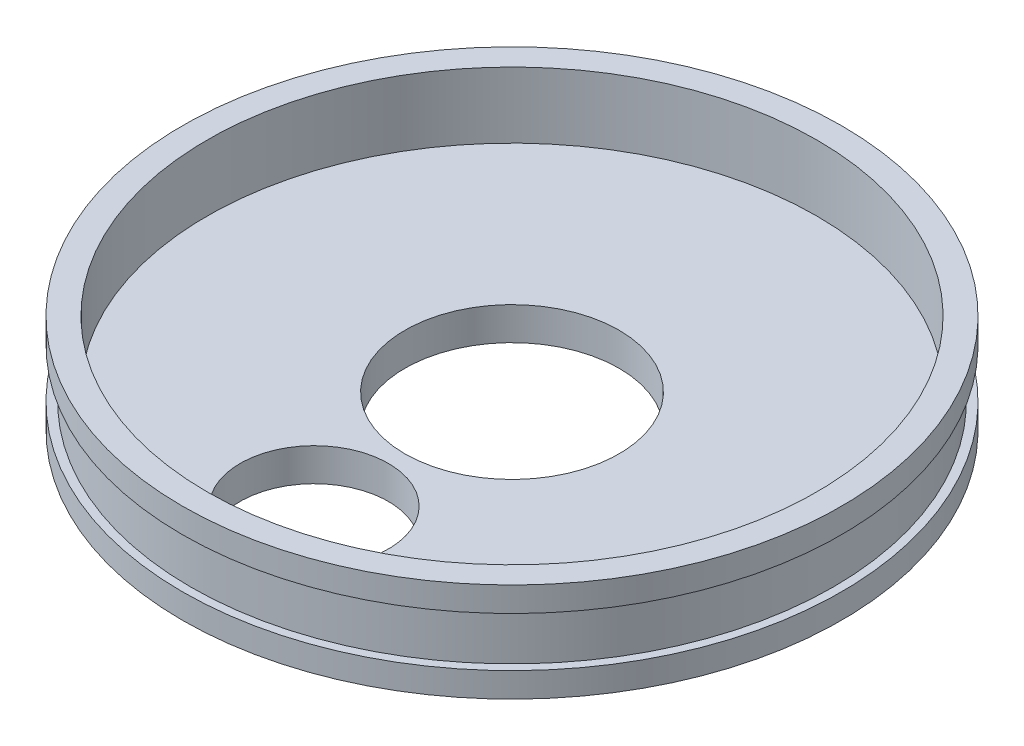
SolidWorks part; units mm, degrees
ref_plane "Front Plane" through (0, 0, 0) normal (0, 0, 1) x (1, 0, 0)
ref_plane "Top Plane" through (0, 0, 0) normal (0, 1, 0) x (1, 0, 0)
ref_plane "Right Plane" through (0, 0, 0) normal (1, 0, 0) x (0, 0, -1)
sketch "Sketch2" plane through (0, 0, 0) normal (0, 1, 0) x (1, 0, 0)
  line L0 (0, 0) -> (0, -12) construction
  circle A0 centre (0, 0) radius 18.5
  circle A1 centre (0, 0) radius 20
  circle A2 centre (0, 0) radius 17.5 construction
  circle A3 centre (0, -12) radius 4.5
  circle A4 centre (0, 0) radius 6.5
  dimension "D1" = 37
  dimension "D2" = 40
  dimension "D3" = 35
  dimension "D5" = 9
  dimension "D6" = 13
  dimension "D4" = 12
extrude "LidBase" add sketch "Sketch2" along normal blind 2 contours A1 A0 | A0 A3 region at (-17.9767, 0, 0) region at (-19.4343, 0, 0)
extrude "LidWalls" add sketch "Sketch2<4>" along normal blind 6 contours A1 A0 region at (-19.4343, 0, 0)
sketch "Sketch2<4>" plane through (0, 0, 0) normal (0, 1, 0) x (1, 0, 0) same geometry as "Sketch2"
sketch "Sketch3" plane through (0, 0, 0) normal (1, 0, 0) x (0, 0, -1)
  line L0 (0, 0) -> (0, 6) construction
  line L1 (19.5, 4.5) -> (20, 4.5)
  line L2 (18.5, 6) -> (-18.5, 6) construction
  line L3 (0, 0) -> (20, 0) construction
  line L4 (20, 0) -> (20, 1.5) construction
  line L5 (20, 1.5) -> (19.5, 1.5)
  line L6 (19.5, 1.5) -> (19.5, 4.5)
  line L7 (20, 4.5) -> (20, 1.5)
  line L9 (20, 0) -> (20, 6) construction
  line L11 (20, 6) -> (0, 6) construction
  dimension "D1" = 6
  dimension "D2" = 1.5
  dimension "D3" = 0.5
  dimension "D4" = 3
revolve "Beltgrooves" cut sketch "Sketch3" angle 360 about L0
